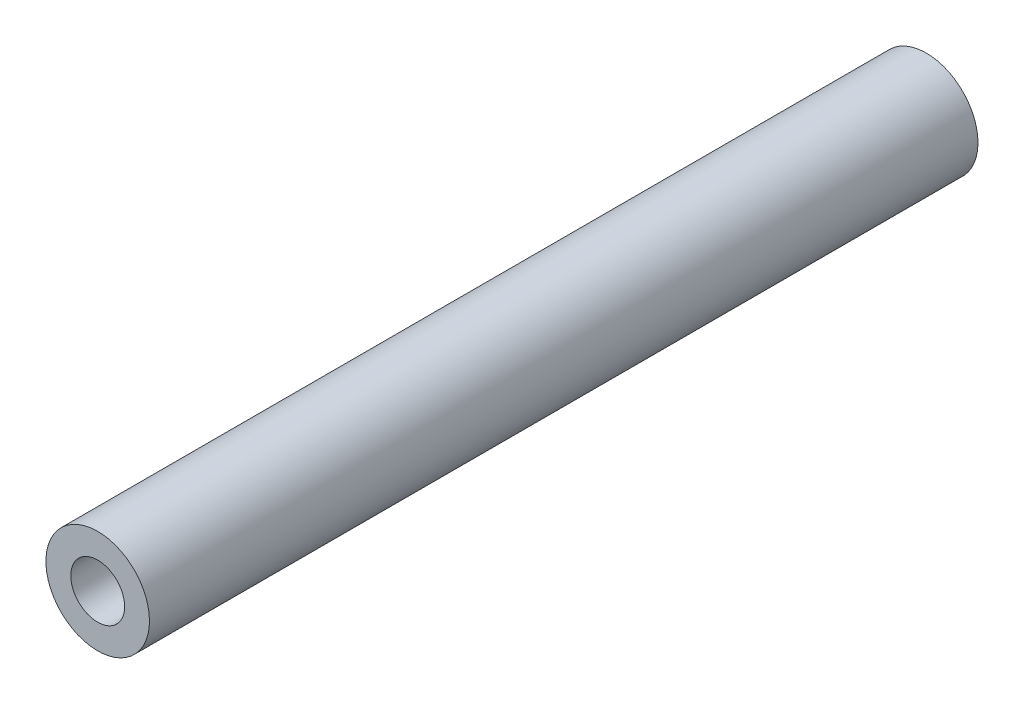
SolidWorks part; units mm, degrees
ref_plane "Front Plane" through (0, 0, 0) normal (0, 0, 1) x (1, 0, 0)
ref_plane "Top Plane" through (0, 0, 0) normal (0, 1, 0) x (1, 0, 0)
ref_plane "Right Plane" through (0, 0, 0) normal (1, 0, 0) x (0, 0, -1)
sketch "Sketch1" plane through (0, 0, 0) normal (0, 0, 1) x (1, 0, 0)
  line L0 (0, 3.302) -> (0, 6.35) construction
  line L1 (0, -3.302) -> (0, -6.35) construction
  circle A0 centre (0, 0) radius 6.35
  circle A1 centre (0, 0) radius 3.302
  dimension "OD" = 12.7
  dimension "ID" = 6.604
sketch "Sketch2" plane through (0, 0, 0) normal (1, 0, 0) x (0, 0, -1)
  line L0 (-50.8, 3.302) -> (50.8, 3.302) construction
  line L1 (-50.8, -3.302) -> (50.8, -3.302) construction
  line L2 (-50.8, -6.35) -> (50.8, -6.35) construction
  line L3 (-50.8, 6.35) -> (50.8, 6.35) construction
  dimension "Length" = 101.6
extrude "Extrude1" add sketch "Sketch1" along normal up to vertex (50.8 mm away) and the other way up to vertex (50.8 mm away) up to point (0, 3.302, 50.8) other way up to point (0, 3.302, -50.8)
sketch "Sketch3" plane through (0, 0, 50.8) normal (0, 0, 1) x (1, 0, 0)
  circle A0 centre (0, 0) radius 3.302 construction
  circle A3 centre (0, 0) radius 3.302
  point P3 (-3.302, 0)
